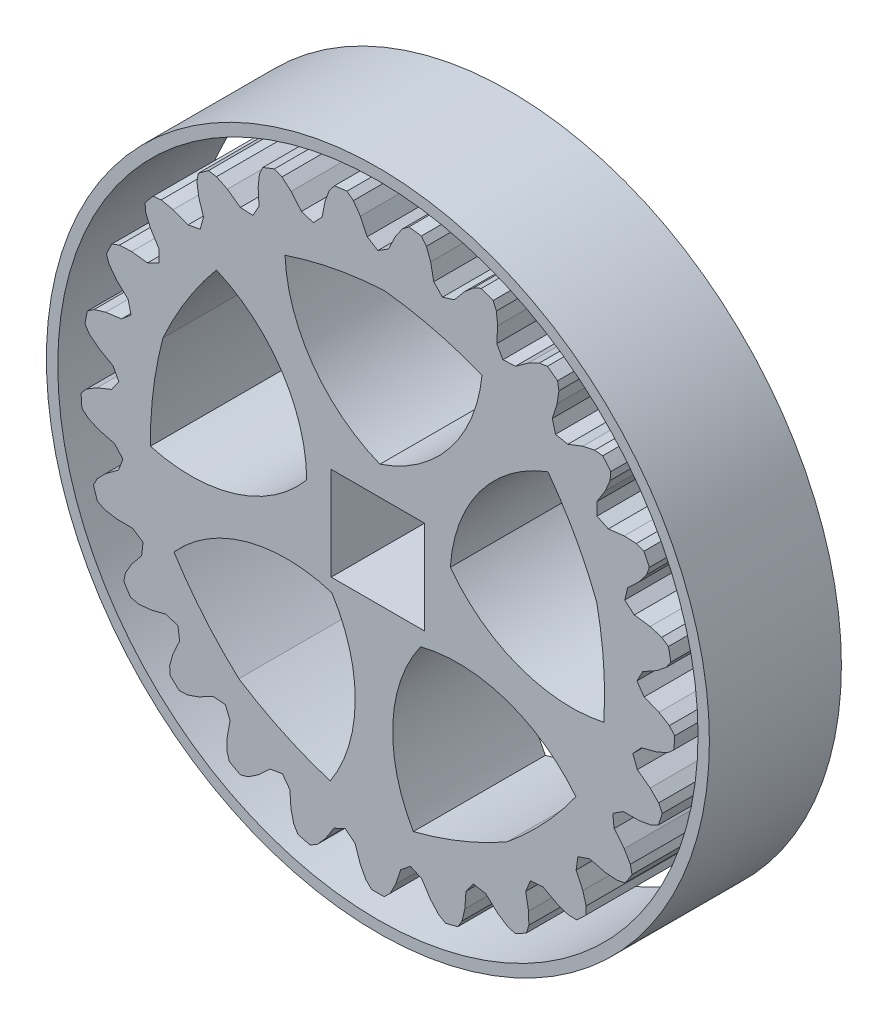
SolidWorks part; units mm, degrees
ref_plane "Front Plane" through (0, 0, 0) normal (0, 0, 1) x (1, 0, 0)
ref_plane "Top Plane" through (0, 0, 0) normal (0, 1, 0) x (1, 0, 0)
ref_plane "Right Plane" through (0, 0, 0) normal (1, 0, 0) x (0, 0, -1)
sketch "Sketch1" plane through (0, 0, 0) normal (0, 0, 1) x (1, 0, 0)
  line L1 (3.5355, -3.5355) -> (-3.5355, -3.5355)
  line L2 (3.5355, -3.5355) -> (3.5355, 3.5355)
  line L3 (3.5355, 3.5355) -> (-3.5355, 3.5355)
  line L4 (-3.5355, -3.5355) -> (-3.5355, 3.5355)
  line L5 (3.5355, -3.5355) -> (-3.5355, 3.5355) construction
  line L6 (3.5355, 3.5355) -> (-3.5355, -3.5355) construction
  circle A0 centre (0, 0) radius 22.5
  circle A1 centre (0, 0) radius 5 construction
  dimension "D1" = 45
  dimension "D2" = 10
extrude "Boss-Extrude1" add sketch "Sketch1" along normal blind 10
sketch "Sketch2" plane through (0, 0, 0) normal (0, 0, 1) x (1, 0, 0)
  line L0 (0, 0) -> (0, 24.257) construction
  line L1 (0, 19.6589) -> (-0.8069, 20.1573)
  line L2 (-0.8069, 20.1573) -> (-1.33, 21.2471)
  line L3 (-1.33, 21.2471) -> (-1.8557, 22.0027)
  line L4 (-1.8557, 22.0027) -> (-2.3453, 22.3774)
  line L5 (-2.3453, 22.3774) -> (-1.8557, 23.6611)
  line L6 (-1.8557, 23.6611) -> (0, 24.257)
  line L7 (1.8557, 23.6611) -> (0, 24.257)
  line L8 (2.3453, 22.3774) -> (1.8557, 23.6611)
  line L9 (1.8557, 22.0027) -> (2.3453, 22.3774)
  line L10 (1.33, 21.2471) -> (1.8557, 22.0027)
  line L11 (0.8069, 20.1573) -> (1.33, 21.2471)
  line L12 (0, 19.6589) -> (0.8069, 20.1573)
  circle A22 centre (0, 0) radius 22.5 construction
  point P15 (-0.2909, 20.2816)
  point P16 (0, 19.6589)
  point P17 (-0.9615, 21.2236)
  point P18 (-1.2489, 21.8463)
  point P19 (-1.8557, 22.4233)
  point P20 (-1.4724, 22.0698)
  point P21 (-1.8557, 23.6611)
  point P22 (0, 24.257)
  point P23 (-0.5014, 20.2173)
  point P24 (0.8069, 20.1573)
  point P25 (1.33, 21.2471)
  point P26 (1.8557, 22.0027)
  point P28 (2.3453, 22.3774)
extrude "Cut-Extrude1" cut sketch "Sketch2" along normal through all
pattern_circular "CirPattern1" count 25 over 360 about axis through (0, 0, 10) along (0, 0, -1) of "Cut-Extrude1"
sketch "Sketch3" plane through (0, 0, 0) normal (0, 0, 1) x (1, 0, 0)
  circle A0 centre (0, 0) radius 29.75
  dimension "D1" = 59.5
sketch "Sketch4" plane through (0, 0, 0) normal (0, 0, 1) x (1, 0, 0)
  line L0 (0, 0) -> (0.4708, 17.272) construction
  arc A0 (0.1559, 5.7183) -> (-7.0351, 15.8325) centre (4.3693, 16.3273) cw
  arc A1 (0.4708, 17.272) -> (-7.0351, 15.8325) centre (2.0438, -11.2177) ccw
  arc A2 (0.4708, 17.272) -> (7.8871, 15.4257) centre (-2.6519, -11.0897) cw
  arc A3 (0.1559, 5.7183) -> (7.8871, 15.4257) centre (-3.4734, 16.541) ccw
  point P10 (7.927, 13.9467)
  point P11 (-7.1673, 16.8058)
  point P12 (-7.0351, 15.8325)
extrude "Cut-Extrude2" cut sketch "Sketch4" along normal through all both
sketch "Sketch5" plane through (0, 0, 0) normal (0, 0, 1) x (1, 0, 0)
  line L0 (3.5355, -3.5355) -> (-3.5355, 3.5355) construction
  circle A0 centre (0, 0) radius 25.1098
  circle A1 centre (0, 0) radius 24.2496
extrude "Boss-Extrude2" add sketch "Sketch5" along normal blind 10 separate body
pattern_circular "CirPattern2" count 5 over 360 about axis through (0, 0, 10) along (0, 0, -1) of "Cut-Extrude2" reverse direction yes
